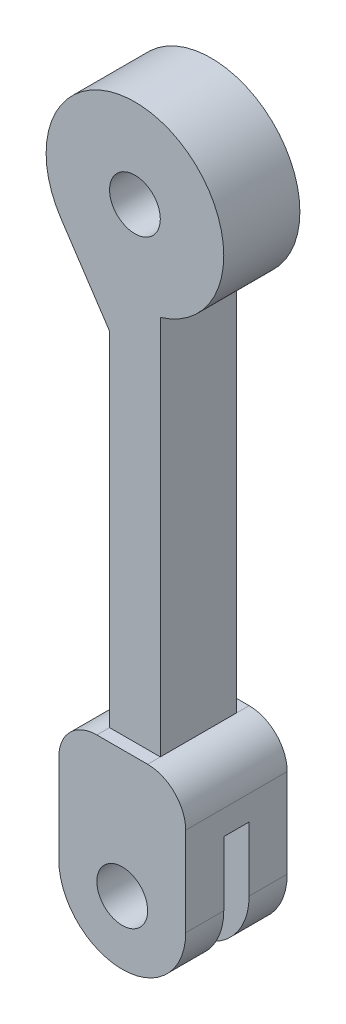
SolidWorks part; units mm, degrees
ref_plane "Front Plane" through (0, 0, 0) normal (0, 0, 1) x (1, 0, 0)
ref_plane "Top Plane" through (0, 0, 0) normal (0, 1, 0) x (1, 0, 0)
ref_plane "Right Plane" through (0, 0, 0) normal (1, 0, 0) x (0, 0, -1)
sketch "Sketch1" plane through (0, 0, 0) normal (0, 0, 1) x (1, 0, 0)
  line L0 (-2.5, 0) -> (-2.5, 3.5)
  line L1 (-1, 5) -> (1, 5)
  line L2 (2.5, 3.5) -> (2.5, 0)
  arc A0 (-2.5, 0) -> (2.5, 0) centre (0, 0) ccw
  circle A1 centre (0, 0) radius 1
  arc A2 (-1, 5) -> (-2.5, 3.5) centre (-1, 3.5) ccw
  arc A3 (2.5, 3.5) -> (1, 5) centre (1, 3.5) ccw
  point P12 (2.5, 5)
  dimension "D1" = 1.5
  dimension "D2" = 2
  dimension "D3" = 5
  dimension "D5" = 1.5
  dimension "D4" = 5
extrude "Boss-Extrude1" add sketch "Sketch1" along normal blind 4
ref_plane "Plane1" through (0, 0, 2) normal (0, 0, 1) x (1, 0, 0)
sketch "Sketch2" plane through (0, 0, 0) normal (0, 0, 1) x (1, 0, 0)
  line L0 (1, 5) -> (1, 20)
  line L1 (-2.917, 21.4198) -> (-1, 18.529)
  line L2 (-1, 18.529) -> (-1, 5)
  line L3 (-1, 5) -> (1, 5)
  line L6 (0, 23.3541) -> (0, 0) construction
  circle A0 centre (0, 23.3541) radius 1
  arc A1 (1, 20) -> (-2.917, 21.4198) centre (0, 23.3541) ccw
  dimension "D1" = 2
  dimension "D2" = 7
  dimension "D3" = 2.4798
  dimension "D4" = 15
extrude "Boss-Extrude2" add sketch "Sketch2" along normal blind 1.5 and the other way blind 1.5 from surface starting at plane "Plane1"
sketch "Sketch3" plane through (2.5, 0, 0) normal (1, 0, 0) x (0, 0, -1)
  line L0 (0, 0) -> (0, 3.5) construction
  line L1 (-1.5, 2.5305) -> (-2.5, 2.5305)
  line L2 (-1.5, 2.5305) -> (-1.5, -3.5462)
  line L3 (-1.5, -3.5462) -> (-2.5, -3.5462)
  line L4 (-2.5, 2.5305) -> (-2.5, -3.5462)
  line L5 (-1.5, 2.5305) -> (-2.5, -3.5462) construction
  line L6 (-1.5, -3.5462) -> (-2.5, 2.5305) construction
  point P4 (-2, -0.5079)
  point P7 (0, 1.75)
  dimension "D1" = 1
  dimension "D2" = 1.5
extrude "Cut-Extrude1" cut sketch "Sketch3" against normal blind 10
